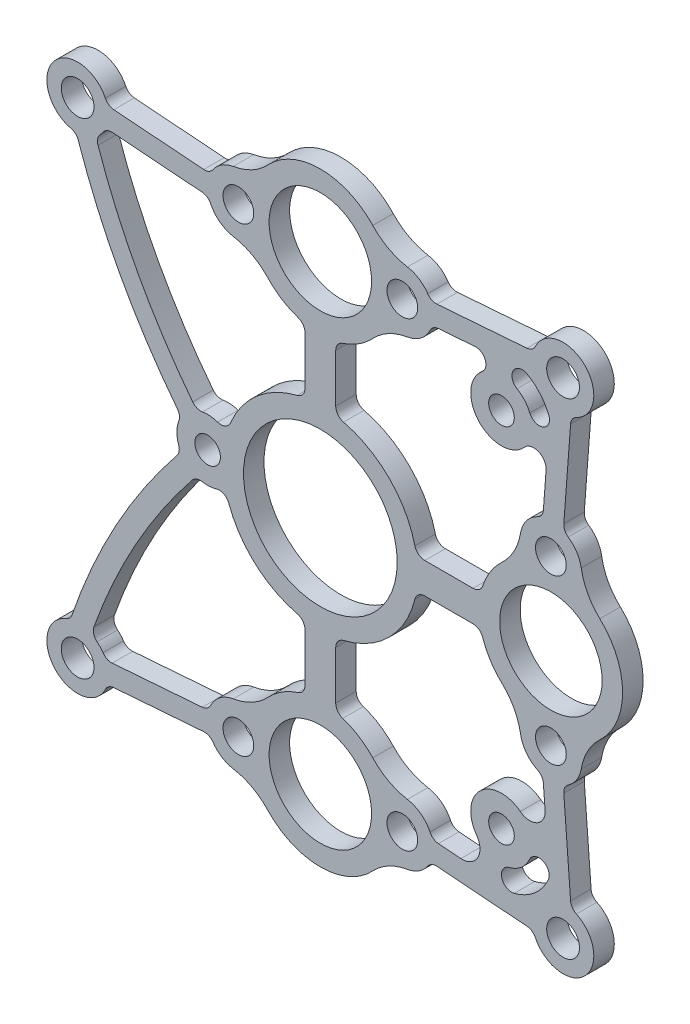
SolidWorks part; units mm, degrees
material "A2017"
ref_plane "正面" through (0, 0, 0) normal (0, 0, 1) x (1, 0, 0)
ref_plane "平面" through (0, 0, 0) normal (0, 1, 0) x (1, 0, 0)
ref_plane "右側面" through (0, 0, 0) normal (1, 0, 0) x (0, 0, -1)
sketch "ｽｹｯﾁ1" plane through (0, 0, 0) normal (0, 0, 1) x (1, 0, 0)
  line L0 (0, 29.5) -> (0, 22.5) construction
  line L1 (-8, 22.5) -> (8, 22.5) construction
  line L2 (29.5, 0) -> (22.5, 0) construction
  line L3 (22.5, 8) -> (22.5, -8) construction
  line L4 (0, -29.5) -> (0, -22.5) construction
  line L5 (8, -22.5) -> (-8, -22.5) construction
  line L6 (-29.5, 0) -> (-22.5, 0) construction
  line L7 (-22.5, -8) -> (-22.5, 8) construction
  circle A1 centre (23.6881, 23.6881) radius 3
  circle A2 centre (23.6881, 23.6881) radius 3
  circle A3 centre (22.5, 0) radius 5
  circle A5 centre (22.5, -8) radius 1.5
  circle A7 centre (0, 22.5) radius 5
  circle A8 centre (0, 22.5) radius 5
  circle A9 centre (0, 0) radius 7.5
  circle A10 centre (0, 0) radius 7.5
  circle A11 centre (8, 22.5) radius 1.5
  circle A12 centre (8, 22.5) radius 1.5
  circle A13 centre (-8, 22.5) radius 1.5
  circle A14 centre (-8, 22.5) radius 1.5
  circle A15 centre (-23.6881, -23.6881) radius 3
  circle A16 centre (-23.6881, -23.6881) radius 3
  circle A17 centre (-23.6881, 23.6881) radius 3
  circle A18 centre (-23.6881, 23.6881) radius 3
  circle A19 centre (23.6881, -23.6881) radius 3
  circle A20 centre (23.6881, -23.6881) radius 3
  circle A21 centre (22.5, 8) radius 1.5
  arc A23 (27.2784, 5.1154) -> (27.2784, -5.1154) centre (22.5, 0) cw
  arc A25 (27.2784, 5.1154) -> (25.458, 8.5) centre (31.3741, 9.5) cw
  arc A27 (27.2784, -5.1154) -> (25.458, -8.5) centre (31.3741, -9.5) ccw
  circle A42 centre (0, 0) radius 9.5
  circle A43 centre (-23.6881, 23.6881) radius 1.6
  circle A44 centre (-23.6881, -23.6881) radius 1.6
  circle A45 centre (23.6881, -23.6881) radius 1.6
  circle A46 centre (23.6881, 23.6881) radius 1.6
  circle A47 centre (-8, 22.5) radius 3 construction
  circle A48 centre (0, 22.5) radius 7 construction
  circle A49 centre (8, 22.5) radius 3 construction
  arc A50 (-5.1154, 27.2784) -> (5.1154, 27.2784) centre (0, 22.5) cw
  arc A51 (-5.1154, 27.2784) -> (-8.5, 25.458) centre (-9.5, 31.3741) cw
  arc A52 (5.1154, 27.2784) -> (8.5, 25.458) centre (9.5, 31.3741) ccw
  arc A53 (-8.5, 25.458) -> (-8.5, 19.542) centre (-8, 22.5) ccw
  arc A54 (8.5, 25.458) -> (8.5, 19.542) centre (8, 22.5) cw
  arc A55 (-5.1154, 17.7216) -> (-8.5, 19.542) centre (-9.5, 13.6259) ccw
  arc A56 (-5.1154, 17.7216) -> (5.1154, 17.7216) centre (0, 22.5) ccw
  arc A57 (5.1154, 17.7216) -> (8.5, 19.542) centre (9.5, 13.6259) cw
  arc A58 (25.458, 8.5) -> (19.542, 8.5) centre (22.5, 8) ccw
  arc A59 (25.458, -8.5) -> (19.542, -8.5) centre (22.5, -8) cw
  arc A60 (17.7216, 5.1154) -> (19.542, 8.5) centre (13.6259, 9.5) ccw
  arc A61 (17.7216, 5.1154) -> (17.7216, -5.1154) centre (22.5, 0) ccw
  arc A62 (17.7216, -5.1154) -> (19.542, -8.5) centre (13.6259, -9.5) cw
  circle A63 centre (22.5, 8) radius 3 construction
  circle A64 centre (22.5, 0) radius 7 construction
  circle A65 centre (22.5, -8) radius 3 construction
  circle A66 centre (0, -22.5) radius 5
  circle A67 centre (-8, -22.5) radius 1.5
  circle A68 centre (8, -22.5) radius 1.5
  arc A69 (5.1154, -27.2784) -> (-5.1154, -27.2784) centre (0, -22.5) cw
  arc A70 (5.1154, -27.2784) -> (8.5, -25.458) centre (9.5, -31.3741) cw
  arc A71 (-5.1154, -27.2784) -> (-8.5, -25.458) centre (-9.5, -31.3741) ccw
  arc A72 (8.5, -25.458) -> (8.5, -19.542) centre (8, -22.5) ccw
  arc A73 (-8.5, -25.458) -> (-8.5, -19.542) centre (-8, -22.5) cw
  arc A74 (5.1154, -17.7216) -> (8.5, -19.542) centre (9.5, -13.6259) ccw
  arc A75 (5.1154, -17.7216) -> (-5.1154, -17.7216) centre (0, -22.5) ccw
  arc A76 (-5.1154, -17.7216) -> (-8.5, -19.542) centre (-9.5, -13.6259) cw
  circle A77 centre (8, -22.5) radius 3 construction
  circle A78 centre (0, -22.5) radius 7 construction
  circle A79 centre (-8, -22.5) radius 3 construction
  circle A80 centre (-22.5, 0) radius 5 [skipped]
  circle A81 centre (-22.5, 8) radius 1.5 [skipped]
  circle A82 centre (-22.5, -8) radius 1.5 [skipped]
  arc A83 (-27.2784, -5.1154) -> (-27.2784, 5.1154) centre (-22.5, 0) cw [skipped]
  arc A84 (-27.2784, -5.1154) -> (-25.458, -8.5) centre (-31.3741, -9.5) cw [skipped]
  arc A85 (-27.2784, 5.1154) -> (-25.458, 8.5) centre (-31.3741, 9.5) ccw [skipped]
  arc A86 (-25.458, -8.5) -> (-19.542, -8.5) centre (-22.5, -8) ccw [skipped]
  arc A87 (-25.458, 8.5) -> (-19.542, 8.5) centre (-22.5, 8) cw [skipped]
  arc A88 (-17.7216, -5.1154) -> (-19.542, -8.5) centre (-13.6259, -9.5) ccw [skipped]
  arc A89 (-17.7216, -5.1154) -> (-17.7216, 5.1154) centre (-22.5, 0) ccw [skipped]
  arc A90 (-17.7216, 5.1154) -> (-19.542, 8.5) centre (-13.6259, 9.5) cw [skipped]
  circle A91 centre (-22.5, -8) radius 3 construction
  circle A92 centre (-22.5, 0) radius 7 construction
  circle A93 centre (-22.5, 8) radius 3 construction
  point P5 (0, -22.5)
  point P6 (33.8316, 4.9454)
  point P59 (-8.5, 22.5)
  point P121 (0, 0)
  point P122 (0, 0)
  point P124 (7.603, 22.5)
  dimension "D15" = 19
  dimension "D16" = 2
  dimension "D17" = 3.2
  dimension "D18" = 14
  dimension "D19" = 6
  dimension "D20" = 6
  dimension "D1" = 0
  dimension "D3" = 4
  dimension "D4" = 0
  dimension "D5" = 0
  dimension "D6" = 0
  dimension "D7" = 0
  dimension "D8" = 0
  dimension "D9" = 0
  dimension "D10" = 0
extrude "ﾎﾞｽ - 押し出し1" add sketch "ｽｹｯﾁ1" against normal blind 2
sketch "ｽｹｯﾁ2" plane through (0, 0, 0) normal (0, 0, 1) x (1, 0, 0)
  circle A0 centre (-11, 0.25) radius 1.5 construction
  circle A1 centre (17.6777, 17.9277) radius 1.5 construction
  circle A2 centre (17.6777, -17.4277) radius 1.5 construction
  circle A3 centre (-11, 0.25) radius 3
  circle A4 centre (17.6777, 17.9277) radius 3
  circle A5 centre (17.6777, -17.4277) radius 3
  dimension "D1" = 3
  dimension "D2" = 6
extrude "ﾎﾞｽ - 押し出し2" add sketch "ｽｹｯﾁ2" against normal through all
hole_wizard "M3 ねじ穴1" positions "ｽｹｯﾁ3" profile "ｽｹｯﾁ4" tap size "M3" standard "JIS" end condition through all
sketch "ｽｹｯﾁ3" plane through (0, 0, 0) normal (0, 0, 1) x (1, 0, 0)
  point P0 (-11, 0.25)
  point P3 (17.6777, 17.9277)
  point P6 (17.6777, -17.4277)
sketch "ｽｹｯﾁ4" plane through (-11, 0.25, 0) normal (1, 0, 0) x (0, -1, 0)
  line L0 (0, 0) -> (0, 2)
  line L1 (0, 2) -> (1.25, 2)
  line L2 (1.25, 2) -> (1.25, 0)
  line L5 (1.25, 0) -> (0, 0)
  line L11 (0, -6.35) -> (0, 107.95) construction
  dimension "次ｻｰﾌｪｽまでのねじ下穴ﾄﾞﾘﾙ直径" = 2.5
  dimension "次ｻｰﾌｪｽまでのねじ下穴ﾄﾞﾘﾙの深さ" = 2
cosmetic thread "穴のねじ山1" parameters "D2"=3
cosmetic thread "穴のねじ山2" parameters "D2"=3
cosmetic thread "穴のねじ山3" parameters "D2"=3
sketch "ｽｹｯﾁ5" plane through (0, 0, 0) normal (0, 0, 1) x (1, 0, 0)
  line L0 (0, 22.5) -> (0, 0) construction
  line L1 (0, 22.5) -> (0, 0) construction
  line L2 (1.5, 22.5) -> (1.5, 0)
  line L3 (-1.5, 22.5) -> (-1.5, 0)
  line L4 (22.5, 0) -> (0, 0) construction
  line L5 (22.5, -1.5) -> (0, -1.5)
  line L6 (22.5, 1.5) -> (0, 1.5)
  line L7 (0, 0) -> (0, -22.5) construction
  line L8 (1.5, 0) -> (1.5, -22.5)
  line L9 (-1.5, 0) -> (-1.5, -22.5)
  arc A0 (1.5, 22.5) -> (-1.5, 22.5) centre (0, 22.5) ccw
  arc A1 (-1.5, 0) -> (1.5, 0) centre (0, 0) ccw
  arc A2 (22.5, -1.5) -> (22.5, 1.5) centre (22.5, 0) ccw
  arc A3 (0, 1.5) -> (0, -1.5) centre (0, 0) ccw
  arc A4 (1.5, 0) -> (-1.5, 0) centre (0, 0) ccw
  arc A5 (-1.5, -22.5) -> (1.5, -22.5) centre (0, -22.5) ccw
  arc A6 (5.1154, -17.7216) -> (-5.1154, -17.7216) centre (0, -22.5) ccw construction
  arc A7 (17.7216, 5.1154) -> (17.7216, -5.1154) centre (22.5, 0) ccw construction
  arc A8 (-5.1154, 17.7216) -> (5.1154, 17.7216) centre (0, 22.5) ccw construction
  arc A9 (-9.2456, -2.1836) -> (-9.1369, 2.6014) centre (0, 0) ccw construction
  arc A10 (5.1154, -17.7216) -> (-5.1154, -17.7216) centre (0, -22.5) ccw
  arc A11 (17.7216, 5.1154) -> (17.7216, -5.1154) centre (22.5, 0) ccw
  arc A12 (-5.1154, 17.7216) -> (5.1154, 17.7216) centre (0, 22.5) ccw
  arc A13 (-9.2456, -2.1836) -> (-9.1369, 2.6014) centre (0, 0) ccw
  point P4 (0, 11.25)
  point P12 (11.25, 0)
  point P17 (0, -11.25)
  point P25 (-1.5, 0)
  arc M19 (-5.1154, 17.7216) -> (5.1154, 17.7216) centre (0, 22.5) ccw
  dimension "D1" = 3
extrude "ﾎﾞｽ - 押し出し3" add sketch "ｽｹｯﾁ5" against normal through all contours A13 L2 L3 M19 | A13 L5 A11 L6 | A13 L9 A10 L8 region at (0, 12.5073, 0) region at (12.5073, 0, 0) region at (0, -12.5073, 0)
sketch "ｽｹｯﾁ6" plane through (0, 0, 0) normal (0, 0, 1) x (1, 0, 0)
  line L0 (8, 22.5) -> (23.6881, 23.6881) construction
  line L1 (7.9245, 23.4971) -> (23.6126, 24.6852)
  line L2 (8.0755, 21.5029) -> (23.7636, 22.6909)
  line L3 (22.5, 8) -> (23.6881, 23.6881) construction
  line L4 (21.5029, 8.0755) -> (22.6909, 23.7636)
  line L5 (23.4971, 7.9245) -> (24.6852, 23.6126)
  line L6 (0, 0) -> (29.5, 0) construction
  line L7 (8, -22.5) -> (23.6881, -23.6881) construction
  line L8 (7.9245, -23.4971) -> (23.6126, -24.6852)
  line L9 (8.0755, -21.5029) -> (23.7636, -22.6909)
  line L10 (22.5, -8) -> (23.6881, -23.6881) construction
  line L11 (21.5029, -8.0755) -> (22.6909, -23.7636)
  line L12 (23.4971, -7.9245) -> (24.6852, -23.6126)
  arc A0 (7.9245, 23.4971) -> (8.0755, 21.5029) centre (8, 22.5) ccw
  arc A1 (23.7636, 22.6909) -> (23.6126, 24.6852) centre (23.6881, 23.6881) ccw
  arc A2 (21.5029, 8.0755) -> (23.4971, 7.9245) centre (22.5, 8) ccw
  arc A3 (24.6852, 23.6126) -> (22.6909, 23.7636) centre (23.6881, 23.6881) ccw
  arc A5 (8.5, 19.542) -> (8.5, 25.458) centre (8, 22.5) ccw construction
  arc A6 (25.458, 8.5) -> (19.542, 8.5) centre (22.5, 8) ccw construction
  circle A7 centre (23.6881, 23.6881) radius 3 construction
  arc A8 (8.5, 19.542) -> (8.5, 25.458) centre (8, 22.5) ccw
  arc A9 (25.458, 8.5) -> (19.542, 8.5) centre (22.5, 8) ccw
  circle A10 centre (23.6881, 23.6881) radius 3
  arc A11 (7.9245, -23.4971) -> (8.0755, -21.5029) centre (8, -22.5) cw
  arc A12 (23.7636, -22.6909) -> (23.6126, -24.6852) centre (23.6881, -23.6881) cw
  arc A13 (21.5029, -8.0755) -> (23.4971, -7.9245) centre (22.5, -8) cw
  arc A14 (24.6852, -23.6126) -> (22.6909, -23.7636) centre (23.6881, -23.6881) cw
  circle A15 centre (23.6881, -23.6881) radius 3
  arc A16 (25.458, -8.5) -> (19.542, -8.5) centre (22.5, -8) cw
  arc A17 (8.5, -19.542) -> (8.5, -25.458) centre (8, -22.5) cw
  arc A18 (27.2784, -5.1154) -> (27.2784, 5.1154) centre (22.5, 0) ccw construction
  point P4 (15.844, 23.094)
  point P12 (23.094, 15.844)
  point P18 (24.9345, 23.5937)
  point P33 (15.844, -23.094)
  point P40 (23.094, -15.844)
  point P53 (29.5, 0)
  circle M10 centre (23.6881, 23.6881) radius 3
  dimension "D1" = 2
extrude "ﾎﾞｽ - 押し出し4" add sketch "ｽｹｯﾁ6" against normal through all contours L12 A16 L11 A15 | L9 A17 L8 A15 | A9 L5 L4 M10 | A8 L2 L1 M10 region at (15.844, 23.094, 0) region at (23.094, 15.844, 0) region at (15.844, -23.094, 0) region at (23.094, -15.844, 0)
sketch "ｽｹｯﾁ7" plane through (0, 0, 0) normal (0, 0, 1) x (1, 0, 0)
  line L0 (10.8959, 21.7164) -> (20.9432, 22.4773) construction
  line L1 (23.6881, 23.6881) -> (17.6777, 17.9277) construction
  line L2 (21.7164, 10.8959) -> (22.4773, 20.9432) construction
  line L3 (20.823, 15.1286) -> (17.6777, 17.9277) construction
  line L4 (17.6777, 17.9277) -> (15.1608, 21.0366) construction
  line L5 (15.1608, 21.0366) -> (20.823, 15.1286) construction
  line L6 (21.7164, 10.8959) -> (22.4773, 20.9432)
  line L7 (10.8959, 21.7164) -> (20.9432, 22.4773)
  line L8 (17.6777, -17.4277) -> (23.6881, -23.6881) construction
  line L9 (10.8959, -21.7164) -> (20.9432, -22.4773) construction
  line L10 (21.7164, -10.8959) -> (22.4773, -20.9432) construction
  line L11 (10.8959, -21.7164) -> (20.9432, -22.4773)
  line L12 (21.7164, -10.8959) -> (22.4773, -20.9432)
  line L13 (13.845, -20.2029) -> (17.6777, -17.4277) construction
  line L14 (17.6777, -17.4277) -> (20.4376, -13.8734) construction
  line L15 (20.4376, -13.8734) -> (13.845, -20.2029) construction
  circle A0 centre (15.1608, 21.0366) radius 1
  circle A1 centre (17.6777, 17.9277) radius 3 construction
  circle A2 centre (17.6777, 17.9277) radius 3
  circle A3 centre (20.823, 15.1286) radius 1.2105
  arc A4 (20.9432, 22.4773) -> (22.4773, 20.9432) centre (23.6881, 23.6881) ccw construction
  arc A5 (20.9432, 22.4773) -> (22.4773, 20.9432) centre (23.6881, 23.6881) ccw
  arc A6 (22.4773, -20.9432) -> (20.9432, -22.4773) centre (23.6881, -23.6881) ccw construction
  circle A7 centre (17.6777, -17.4277) radius 3 construction
  arc A8 (22.4773, -20.9432) -> (20.9432, -22.4773) centre (23.6881, -23.6881) ccw
  circle A9 centre (17.6777, -17.4277) radius 3
  circle A10 centre (20.4376, -13.8734) radius 1.5
  circle A11 centre (13.845, -20.2029) radius 1.732
  dimension "D1" = 2
  dimension "D2" = 3
extrude "ﾎﾞｽ - 押し出し5" add sketch "ｽｹｯﾁ7" against normal through all contours A11 L11 A8 L12 A10 A9 | A5 L7 A0 A2 A3 L6 region at (20.1419, 20.0544, 0) region at (19.7084, -19.7916, 0)
sketch "ｽｹｯﾁ8" plane through (0, 0, 0) normal (0, 0, 1) x (1, 0, 0)
  line L0 (-8, 22.5) -> (-23.6881, 23.6881) construction
  line L1 (-8.0755, 21.5029) -> (-23.7636, 22.6909)
  line L2 (-7.9245, 23.4971) -> (-23.6126, 24.6852)
  line L3 (-8, -22.5) -> (-23.6881, -23.6881) construction
  line L4 (-7.9245, -23.4971) -> (-23.6126, -24.6852)
  line L5 (-8.0755, -21.5029) -> (-23.7636, -22.6909)
  line L6 (-11, 0.25) -> (22.5, 0) construction
  line L18 (10.7448, -23.7107) -> (20.7922, -24.4716)
  line L19 (24.4716, -20.7922) -> (23.7107, -10.7448)
  line L20 (23.7107, 10.7448) -> (24.4716, 20.7922)
  line L21 (20.7922, 24.4716) -> (10.7448, 23.7107)
  line L22 (-1.5, 15.6626) -> (-1.5, 9.3808)
  line L23 (-1.5, -9.3808) -> (-1.5, -15.6626)
  line L24 (10.7448, -23.7107) -> (20.7922, -24.4716)
  line L25 (24.4716, -20.7922) -> (23.7107, -10.7448)
  line L26 (23.7107, 10.7448) -> (24.4716, 20.7922)
  line L27 (20.7922, 24.4716) -> (10.7448, 23.7107)
  line L28 (-1.5, 15.6626) -> (-1.5, 9.3808)
  line L29 (-1.5, -9.3808) -> (-1.5, -15.6626)
  arc A0 (-8.0755, 21.5029) -> (-7.9245, 23.4971) centre (-8, 22.5) ccw
  arc A1 (-23.6126, 24.6852) -> (-23.7636, 22.6909) centre (-23.6881, 23.6881) ccw
  arc A2 (-7.9245, -23.4971) -> (-8.0755, -21.5029) centre (-8, -22.5) ccw
  arc A3 (-23.7636, -22.6909) -> (-23.6126, -24.6852) centre (-23.6881, -23.6881) ccw
  arc A8 (-23.6881, 23.6881) -> (-11, 0.25) centre (34.1027, 39.8195) ccw construction
  circle A9 centre (-23.6881, -23.6881) radius 3 construction
  circle A10 centre (-23.6881, 23.6881) radius 3 construction
  circle A11 centre (-23.6881, -23.6881) radius 3
  circle A12 centre (-23.6881, 23.6881) radius 3
  arc A13 (-24.6513, 23.4192) -> (-11.7517, -0.4095) centre (34.1027, 39.8195) ccw
  arc A14 (-22.7249, 23.9569) -> (-10.2483, 0.9095) centre (34.1027, 39.8195) ccw
  arc A15 (-22.7249, 23.9569) -> (-24.6513, 23.4192) centre (-23.6881, 23.6881) ccw
  arc A16 (-11.7517, -0.4095) -> (-10.2483, 0.9095) centre (-11, 0.25) ccw
  arc A17 (-24.0365, -22.9961) -> (-11, 0.25) centre (33.5072, -39.9882) cw construction
  arc A18 (-24.9955, -22.7129) -> (-11.7418, 0.9206) centre (33.5072, -39.9882) cw
  arc A19 (-23.0774, -23.2793) -> (-10.2582, -0.4206) centre (33.5072, -39.9882) cw
  arc A20 (-23.0774, -23.2793) -> (-24.9955, -22.7129) centre (-24.0365, -22.9961) cw
  arc A21 (-11.7418, 0.9206) -> (-10.2582, -0.4206) centre (-11, 0.25) cw
  arc A33 (8.5, -25.458) -> (10.7448, -23.7107) centre (8, -22.5) ccw
  arc A34 (20.7922, -24.4716) -> (24.4716, -20.7922) centre (23.6881, -23.6881) ccw
  arc A35 (23.7107, -10.7448) -> (25.458, -8.5) centre (22.5, -8) ccw
  arc A36 (27.2784, -5.1154) -> (25.458, -8.5) centre (31.3741, -9.5) ccw
  arc A37 (27.2784, -5.1154) -> (27.2784, 5.1154) centre (22.5, 0) ccw
  arc A38 (25.458, 8.5) -> (27.2784, 5.1154) centre (31.3741, 9.5) ccw
  arc A39 (25.458, 8.5) -> (23.7107, 10.7448) centre (22.5, 8) ccw
  arc A40 (24.4716, 20.7922) -> (20.7922, 24.4716) centre (23.6881, 23.6881) ccw
  arc A41 (10.7448, 23.7107) -> (8.5, 25.458) centre (8, 22.5) ccw
  arc A42 (5.1154, 27.2784) -> (8.5, 25.458) centre (9.5, 31.3741) ccw
  arc A43 (5.1154, 27.2784) -> (-5.1154, 27.2784) centre (0, 22.5) ccw
  arc A44 (-8.5, 25.458) -> (-5.1154, 27.2784) centre (-9.5, 31.3741) ccw
  arc A45 (-8.5, 25.458) -> (-8.5, 19.542) centre (-8, 22.5) ccw
  arc A46 (-5.1154, 17.7216) -> (-8.5, 19.542) centre (-9.5, 13.6259) ccw
  arc A47 (-5.1154, 17.7216) -> (-1.5, 15.6626) centre (0, 22.5) ccw
  arc A48 (-1.5, 9.3808) -> (-9.1369, 2.6014) centre (0, 0) ccw
  arc A49 (-9.1369, 2.6014) -> (-9.2456, -2.1836) centre (-11, 0.25) ccw
  arc A50 (-9.2456, -2.1836) -> (-1.5, -9.3808) centre (0, 0) ccw
  arc A51 (-1.5, -15.6626) -> (-5.1154, -17.7216) centre (0, -22.5) ccw
  arc A52 (-8.5, -19.542) -> (-5.1154, -17.7216) centre (-9.5, -13.6259) ccw
  arc A53 (-8.5, -19.542) -> (-8.5, -25.458) centre (-8, -22.5) ccw
  arc A54 (-5.1154, -27.2784) -> (-8.5, -25.458) centre (-9.5, -31.3741) ccw
  arc A55 (-5.1154, -27.2784) -> (5.1154, -27.2784) centre (0, -22.5) ccw
  arc A56 (8.5, -25.458) -> (5.1154, -27.2784) centre (9.5, -31.3741) ccw
  arc A57 (8.5, -25.458) -> (10.7448, -23.7107) centre (8, -22.5) ccw
  arc A58 (20.7922, -24.4716) -> (24.4716, -20.7922) centre (23.6881, -23.6881) ccw
  arc A59 (23.7107, -10.7448) -> (25.458, -8.5) centre (22.5, -8) ccw
  arc A60 (27.2784, -5.1154) -> (25.458, -8.5) centre (31.3741, -9.5) ccw
  arc A61 (27.2784, -5.1154) -> (27.2784, 5.1154) centre (22.5, 0) ccw
  arc A62 (25.458, 8.5) -> (27.2784, 5.1154) centre (31.3741, 9.5) ccw
  arc A63 (25.458, 8.5) -> (23.7107, 10.7448) centre (22.5, 8) ccw
  arc A64 (24.4716, 20.7922) -> (20.7922, 24.4716) centre (23.6881, 23.6881) ccw
  arc A65 (10.7448, 23.7107) -> (8.5, 25.458) centre (8, 22.5) ccw
  arc A66 (5.1154, 27.2784) -> (8.5, 25.458) centre (9.5, 31.3741) ccw
  arc A67 (5.1154, 27.2784) -> (-5.1154, 27.2784) centre (0, 22.5) ccw
  arc A68 (-8.5, 25.458) -> (-5.1154, 27.2784) centre (-9.5, 31.3741) ccw
  arc A69 (-8.5, 25.458) -> (-8.5, 19.542) centre (-8, 22.5) ccw
  arc A70 (-5.1154, 17.7216) -> (-8.5, 19.542) centre (-9.5, 13.6259) ccw
  arc A71 (-5.1154, 17.7216) -> (-1.5, 15.6626) centre (0, 22.5) ccw
  arc A72 (-1.5, 9.3808) -> (-9.1369, 2.6014) centre (0, 0) ccw
  arc A73 (-9.1369, 2.6014) -> (-9.2456, -2.1836) centre (-11, 0.25) ccw
  arc A74 (-9.2456, -2.1836) -> (-1.5, -9.3808) centre (0, 0) ccw
  arc A75 (-1.5, -15.6626) -> (-5.1154, -17.7216) centre (0, -22.5) ccw
  arc A76 (-8.5, -19.542) -> (-5.1154, -17.7216) centre (-9.5, -13.6259) ccw
  arc A77 (-8.5, -19.542) -> (-8.5, -25.458) centre (-8, -22.5) ccw
  arc A78 (-5.1154, -27.2784) -> (-8.5, -25.458) centre (-9.5, -31.3741) ccw
  arc A79 (-5.1154, -27.2784) -> (5.1154, -27.2784) centre (0, -22.5) ccw
  arc A80 (8.5, -25.458) -> (5.1154, -27.2784) centre (9.5, -31.3741) ccw
  point P4 (-15.844, 23.094)
  point P9 (-15.844, -23.094)
  point P18 (-18.6619, 11.2556)
  point P27 (-18.8253, -10.64)
  point P32 (-18.8273, 11.2545)
  dimension "D3" = 60
  dimension "D1" = 2
  dimension "D2" = 0
extrude "ﾎﾞｽ - 押し出し6" add sketch "ｽｹｯﾁ8" against normal through all contours A73 A12 | A69 L2 A12 L1 | A73 A14 A11 | A77 L5 A11 L4 region at (-15.844, 23.094, 0) region at (-18.3988, 11.398, 0) region at (-18.6986, -11.0584, 0) region at (-15.844, -23.094, 0)
sketch "ｽｹｯﾁ9" plane through (0, 0, 0) normal (0, 0, 1) x (1, 0, 0)
  line L0 (10.8959, 21.7164) -> (15.0853, 22.0337) construction
  line L1 (15.0853, 22.0337) -> (22.603, 22.603) construction
  line L2 (22.603, 22.603) -> (22.0198, 14.9011) construction
  line L3 (21.7164, 10.8959) -> (22.0301, 15.0372) construction
  line L4 (22.0198, 14.9011) -> (21.7164, 10.8959) construction
  line L5 (13.7142, -21.9299) -> (22.603, -22.603) construction
  line L6 (22.603, -22.603) -> (21.9334, -13.7602) construction
  line L7 (21.7164, -10.8959) -> (21.9334, -13.7602) construction
  line L8 (10.8959, -21.7164) -> (13.7142, -21.9299) construction
  arc A0 (19.6977, 21.3802) -> (21.3638, 19.4811) centre (17.6777, 17.9277) cw construction
  arc A1 (22.2853, 19.8694) -> (20.2027, 22.2433) centre (17.6777, 17.9277) ccw
  arc A2 (20.4422, 19.0927) -> (19.1927, 20.517) centre (17.6777, 17.9277) ccw
  arc A3 (20.4422, 19.0927) -> (22.2853, 19.8694) centre (21.3638, 19.4811) ccw
  arc A4 (20.2027, 22.2433) -> (19.1927, 20.517) centre (19.6977, 21.3802) ccw
  circle A5 centre (17.6777, 17.9277) radius 3 construction
  circle A6 centre (17.6777, -17.4277) radius 3 construction
  arc A7 (21.3315, -19.0555) -> (18.671, -21.3024) centre (17.6777, -17.4277) cw construction
  arc A8 (18.9193, -22.2711) -> (22.245, -19.4624) centre (17.6777, -17.4277) ccw
  arc A9 (18.4227, -20.3337) -> (20.4181, -18.6485) centre (17.6777, -17.4277) ccw
  arc A10 (18.4227, -20.3337) -> (18.9193, -22.2711) centre (18.671, -21.3024) ccw
  arc A11 (22.245, -19.4624) -> (20.4181, -18.6485) centre (21.3315, -19.0555) ccw
  point P4 (20.6846, 20.5656)
  point P37 (20.2586, -20.4837)
  point P42 (0, 0)
  dimension "D1" = 2
  dimension "D2" = 2
extrude "ｶｯﾄ - 押し出し1" cut sketch "ｽｹｯﾁ9" against normal up to surface (2 mm away) up to face at (-10.4688, -14.7595, -2)
fillet "ﾌｨﾚｯﾄ1" radius 1 42 edges at (1.5, -15.6626, -1) (1.5, -9.3808, -1) (9.3808, -1.5, -1) (15.6626, -1.5, -1) (21.7164, -10.8959, -1) (10.8959, -21.7164, -1) (21.7164, 10.8959, -1) (15.6626, 1.5, -1) (9.3808, 1.5, -1) (1.5, 9.3808, -1) (1.5, 15.6626, -1) (10.8959, 21.7164, -1) (-20.7922, -24.4716, -1) (-10.7448, -23.7107, -1) (10.7448, -23.7107, -1) (20.7922, -24.4716, -1) (24.4716, -20.7922, -1) (23.7107, -10.7448, -1) (23.7107, 10.7448, -1) (24.4716, 20.7922, -1) (20.7922, 24.4716, -1) (10.7448, 23.7107, -1) (-10.7448, 23.7107, -1) (-23.8205, 20.691, -1) (-13.5819, 1.7777, -1) (-13.6044, -1.239, -1) (-24.3865, -20.7705, -1) (-1.5, 15.6626, -1) (-1.5, 9.3808, -1) (-9.1369, 2.6014, -1) (-12.0474, 3.0612, -1) (-21.9068, 21.2741, -1) (-20.9432, 22.4773, -1) (-10.8959, 21.7164, -1) (-22.3541, -21.001, -1) (-12.0892, -2.5453, -1) (-9.2456, -2.1836, -1) (-1.5, -9.3808, -1) (-1.5, -15.6626, -1) (-10.8959, -21.7164, -1) (-20.9432, -22.4773, -1) (-20.7922, 24.4716, -1)
